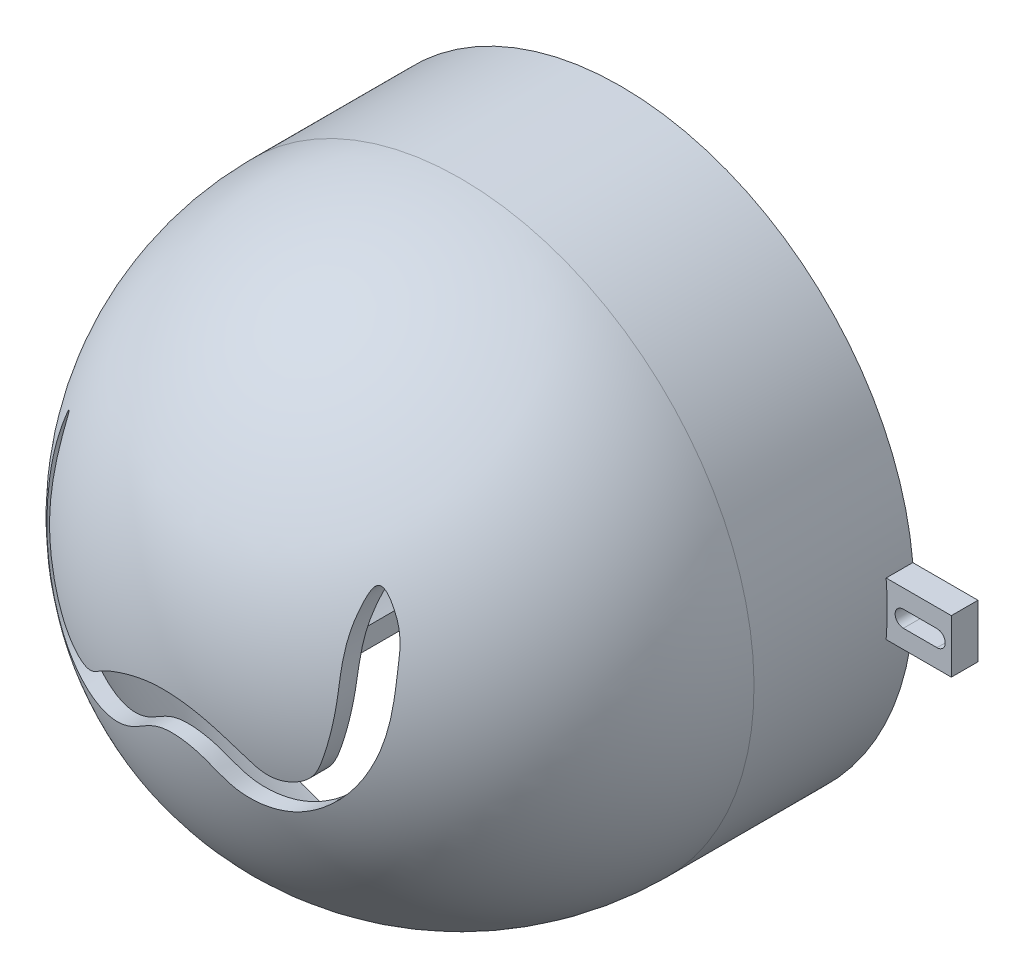
SolidWorks part; units mm, degrees
ref_plane "Front Plane" through (0, 0, 0) normal (0, 0, 1) x (1, 0, 0)
ref_plane "Top Plane" through (0, 0, 0) normal (0, 1, 0) x (1, 0, 0)
ref_plane "Right Plane" through (0, 0, 0) normal (1, 0, 0) x (0, 0, -1)
sketch "Sketch2" plane through (0, 0, 0) normal (1, 0, 0) x (0, 0, -1)
  line L7 (65.5803, 0) -> (147.5803, 0)
  line L8 (147.5803, 0) -> (147.5803, 52)
  line L9 (147.5803, 52) -> (117.5803, 52)
  line L10 (117.5803, 52) -> (117.5803, 0) construction
  line L11 (65.5803, 0) -> (46.7658, 0) construction
  arc A1 (117.5803, 52) -> (65.5803, 0) centre (117.5803, 0) ccw
  dimension "D4" = 52
  dimension "D3" = 30
revolve "Revolve1" add sketch "Sketch2" angle 360 about L11
shell "Shell1" thickness 3 removed face at (-52, 0, -147.5803) outward yes
sketch "Sketch5" plane through (0, 0, 0) normal (0, 1, 0) x (1, 0, 0)
  line L0 (-55, 147.5803) -> (55, 147.5803) construction
  line L1 (55, 147.5803) -> (-55, 147.5803) construction
  line L2 (0, 147.5803) -> (0, 100.0199) construction
  line L4 (-32, 147.5803) -> (32, 147.5803)
  line L5 (-32, 147.5803) -> (-32, 106.5803)
  line L6 (-32, 106.5803) -> (32, 106.5803)
  line L7 (32, 147.5803) -> (32, 106.5803)
  point P12 (0, 147.5803)
  dimension "D1" = 64
  dimension "D2" = 41
extrude "Cut-Extrude2" cut sketch "Sketch5" against normal through all
ref_plane "Plane1" through (0, 0, -67.5803) normal (0, 0, -1) x (-1, 0, 0)
sketch "Sketch6" plane through (0, 0, -67.5803) normal (0, 0, -1) x (-1, 0, 0)
  line L0 (-228.021, 103.0378) -> (28.6456, 103.0378) construction
  spline S0 degree 3 poles (38.3471, 11.2509) (35.0848, 22.9055) (35.9096, 5.5718) (31.5895, -1.502) (25.9695, -8.3833) (18.7391, -9.3823) (14.7522, -5.8381) (9.7363, -2.9172) (3.2802, -0.5319) (-5.0447, -1.072) (-11.3051, -4.593) (-16.5079, -9.0906) (-22.1404, -7.1939) (-24.3491, -1.0805) (-25.8221, 8.4528) (-24.4951, 15.7489) (-26.4408, 24.8164) (-30.8169, 18.7026) (-31.5122, 13.3967) (-31.9756, 5.2105) (-30.0828, -2.5083) (-25.5142, -9.9514) (-18.1962, -14.9627) (-9.9902, -13.2705) (-5.595, -8.302) (2.2717, -6.7216) (8.0788, -12.0522) (15.5862, -14.9973) (22.7873, -14.4911) (29.1823, -11.5958) (32.7754, -6.7649) (35.9777, -1.1731) (37.4709, 5.4549) (38.3471, 11.2509) (35.0848, 22.9055) (35.9096, 5.5718) knots -0.084591 -0.055 -0.0249 0 0.047543 0.086529 0.127343 0.150207 0.169698 0.191841 0.224466 0.255222 0.294003 0.315121 0.337438 0.355619 0.394721 0.455796 0.466209 0.484862 0.513641 0.548093 0.583361 0.613542 0.658237 0.684747 0.711698 0.740677 0.774665 0.805471 0.841451 0.862828 0.892573 0.915409 0.945 0.9751 1 1.047543 1.086529 1.127343 only from (36.1408, 18.0279) to (36.1408, 18.0279)
extrude "Cut-Extrude3" cut sketch "Sketch6" against normal through all both and the other way through all
ref_plane "Plane2" through (0, 0, -147.5803) normal (0, 0, -1) x (-1, 0, 0)
ref_plane "Plane3" through (0, 0, -147.5803) normal (0, 0, -1) x (-1, 0, 0)
sketch "Sketch7" plane through (0, 0, -147.5803) normal (0, 0, -1) x (-1, 0, 0)
  line L1 (-67, 0) -> (-67, 5)
  line L2 (-67, 0) -> (-67, -5)
  line L3 (-67, 5) -> (-51.7591, 5)
  line L4 (-51.7591, 5) -> (-52, 0)
  line L5 (-51.7591, -5) -> (-67, -5)
  line L7 (-51.7591, -5) -> (-52, 0)
  line L8 (51.7591, -5) -> (67, -5)
  line L9 (67, 0) -> (67, -5)
  line L10 (67, 0) -> (67, 5)
  line L11 (67, 5) -> (51.7591, 5)
  line L12 (51.7591, 5) -> (52, 0)
  line L13 (51.7591, -5) -> (52, 0)
  arc A0 (32, -40.9878) -> (-32, -40.9878) centre (0, 0) ccw construction
  arc A1 (32, -40.9878) -> (-32, -40.9878) centre (0, 0) ccw construction
  dimension "D1" = 15
  dimension "D2" = 5
  dimension "D3" = 5
extrude "Boss-Extrude1" add sketch "Sketch7" against normal blind 5
sketch "Sketch8" plane through (0, 0, -147.5803) normal (0, 0, -1) x (-1, 0, 0)
  line L0 (-64.3096, 0) -> (-58.0068, 0) construction
  line L1 (-64.3096, 1.55) -> (-58.0068, 1.55)
  line L2 (-64.3096, -1.55) -> (-58.0068, -1.55)
  line L4 (64.3096, 0) -> (58.0068, 0) construction
  line L5 (64.3096, 1.55) -> (58.0068, 1.55)
  line L6 (64.3096, -1.55) -> (58.0068, -1.55)
  arc A0 (-64.3096, 1.55) -> (-64.3096, -1.55) centre (-64.3096, 0) ccw
  arc A1 (-58.0068, -1.55) -> (-58.0068, 1.55) centre (-58.0068, 0) ccw
  arc A2 (64.3096, 1.55) -> (64.3096, -1.55) centre (64.3096, 0) cw
  arc A3 (58.0068, -1.55) -> (58.0068, 1.55) centre (58.0068, 0) cw
  point P3 (-61.1582, 0)
  point P10 (61.1582, 0)
  dimension "D1" = 1.55
extrude "Cut-Extrude4" cut sketch "Sketch8" against normal blind 5
